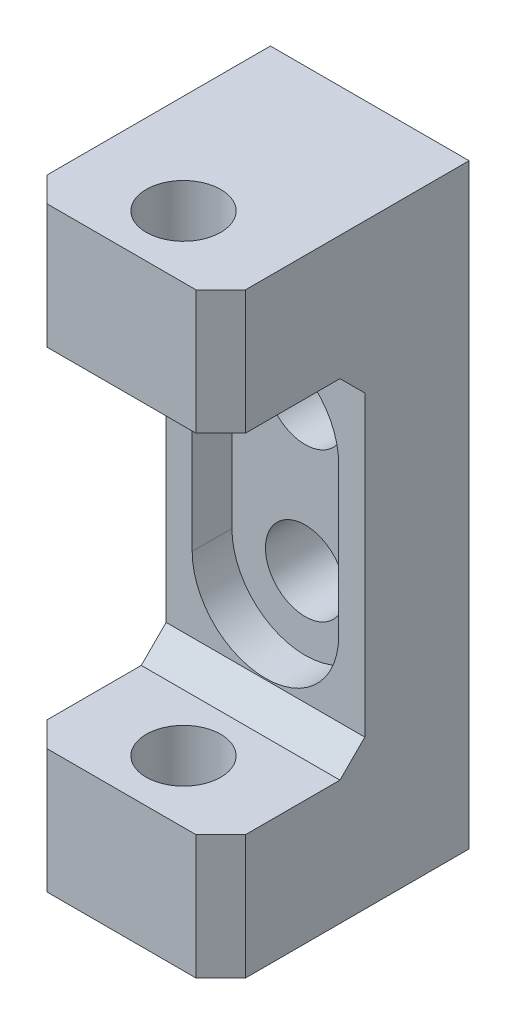
SolidWorks part; units mm, degrees
ref_plane "前视基准面" through (0, 0, 0) normal (0, 0, 1) x (1, 0, 0)
ref_plane "上视基准面" through (0, 0, 0) normal (0, 1, 0) x (1, 0, 0)
ref_plane "右视基准面" through (0, 0, 0) normal (1, 0, 0) x (0, 0, -1)
sketch "草图2" plane through (0, 0, 0) normal (0, 0, 1) x (1, 0, 0)
  line L0 (75, 105) -> (130, 105) construction
  line L1 (104, 105) -> (96, 105)
  line L2 (104, 105) -> (104, 81)
  line L3 (104, 81) -> (96, 81)
  line L4 (96, 105) -> (96, 81)
  line L6 (100, 81) -> (100, 105) construction
  line L7 (130, 105) -> (130, -105) construction
  dimension "D1" = 24
  dimension "D2" = 8
  dimension "D3" = 30
extrude "凸台-拉伸1" add sketch "草图2" along normal blind 10
sketch "草图3" plane through (96, 0, 0) normal (-1, 0, 0) x (0, 0, 1)
  line L0 (0, 93) -> (22.6575, 93) construction
  line L5 (0, 105) -> (0, 81) construction
  line L6 (10, 81) -> (0, 81) construction
  line L7 (4.2, 100) -> (13.3805, 100)
  line L8 (4.2, 100) -> (4.2, 86)
  line L9 (4.2, 86) -> (13.3805, 86)
  line L10 (13.3805, 100) -> (13.3805, 86)
  line L11 (4.2, 100) -> (13.3805, 86) construction
  line L12 (4.2, 86) -> (13.3805, 100) construction
  point P0 (8.7902, 93)
  dimension "D1" = 4.2
  dimension "D2" = 5
extrude "切除-拉伸1" cut sketch "草图3" against normal blind 40
sketch "草图4" plane through (0, 0, 4.2) normal (0, 0, 1) x (1, 0, 0)
  line L0 (100, 100) -> (100, 86) construction
  line L1 (104, 100) -> (96, 100) construction
  line L2 (104, 86) -> (96, 86) construction
  line L3 (100, 93) -> (104, 93) construction
  line L4 (104, 100) -> (104, 86) construction
  circle A0 centre (100, 96) radius 2
  circle A1 centre (100, 90) radius 2
  dimension "D1" = 4
  dimension "D2" = 6
chamfer "倒角1" distance 1 angle 45 2 edges at (100, 86, 4.2) (100, 100, 4.2)
sketch "草图6" plane through (0, 105, 0) normal (0, 1, 0) x (1, 0, 0)
  line L0 (100, -5.2) -> (100, -10) construction
  line L4 (104, -10) -> (104, -5.2)
  line L5 (104, -5.2) -> (96, -5.2)
  line L6 (96, -5.2) -> (96, -10)
  line L7 (96, -10) -> (104, -10)
  line L8 (104, -10) -> (104, -5.2) construction
  line L9 (104, -5.2) -> (96, -5.2) construction
  line L10 (96, -5.2) -> (96, -10) construction
  line L11 (96, -10) -> (104, -10) construction
  circle A1 centre (100, -7.5) radius 1.5
  dimension "D2" = 3
  dimension "D3" = 2.5
  dimension "D1" = 0
hole_wizard "M3 六角头螺栓的柱形沉头孔1" positions "草图7" profile "草图8" counterbore size "M3" standard "GB" end condition through all
sketch "草图7" plane through (124.3639, -131.0101, 4.2) normal (0, 0, 1) x (0, 1, 0)
  point P0 (221.0101, 24.3639)
  point P3 (227.0101, 24.3639)
sketch "草图8" plane through (100, 90, 4.2) normal (1, 0, 0) x (0, -1, 0)
  line L0 (0, 0) -> (0, 4.2)
  line L1 (0, 4.2) -> (1.6, 4.2)
  line L2 (1.6, 4.2) -> (1.6, 1.6)
  line L3 (1.6, 1.6) -> (2.95, 1.6)
  line L4 (2.95, 1.6) -> (2.95, 0)
  line L5 (2.95, 0) -> (0, 0)
  line L6 (0, -6.35) -> (0, 107.95) construction
  dimension "通孔孔直径" = 3.2
  dimension "通孔孔深度" = 4.2
  dimension "柱形沉头孔直径" = 5.9
  dimension "柱形沉头孔深度" = 1.6
sketch "草图11" plane through (0, 0, 4.2) normal (0, 0, 1) x (1, 0, 0)
  line L0 (100, 90) -> (100, 96) construction
  line L1 (97.05, 90) -> (97.05, 96)
  line L2 (102.95, 90) -> (102.95, 96)
  arc A0 (97.05, 90) -> (102.95, 90) centre (100, 90) ccw
  arc A1 (102.95, 96) -> (97.05, 96) centre (100, 96) ccw
  point P2 (100, 93)
  dimension "D1" = 5.9
extrude "切除-拉伸2" cut sketch "草图11" against normal up to surface (1.6 mm away) up to face at (101.6, 90, 2.6)
hole_wizard "大小mm 暗销孔2" positions "草图12" profile "草图13" hole size "Ø3.0" standard "GB"
sketch "草图12" plane through (124.3639, 105, -5) normal (0, 1, 0) x (-1, 0, 0)
  point P0 (24.3639, 12.5)
sketch "草图13" plane through (100, 105, 7.5) normal (1, 0, 0) x (0, 0, 1)
  line L0 (0, 0) -> (0, 24.9013)
  line L1 (0, 24.9013) -> (1.5, 24)
  line L2 (1.5, 24) -> (1.5, 0)
  line L3 (1.5, 0) -> (0, 0)
  line L4 (0, 24.9013) -> (-1.5, 24) construction
  line L5 (0, -6.35) -> (0, 107.95) construction
  dimension "孔直径" = 3
  dimension "孔深度" = 24
  dimension "导头角度" = 118
chamfer "倒角2" distance 1 angle 45 4 edges at (96, 83.5, 10) (104, 83.5, 10) (104, 102.5, 10) (96, 102.5, 10)
